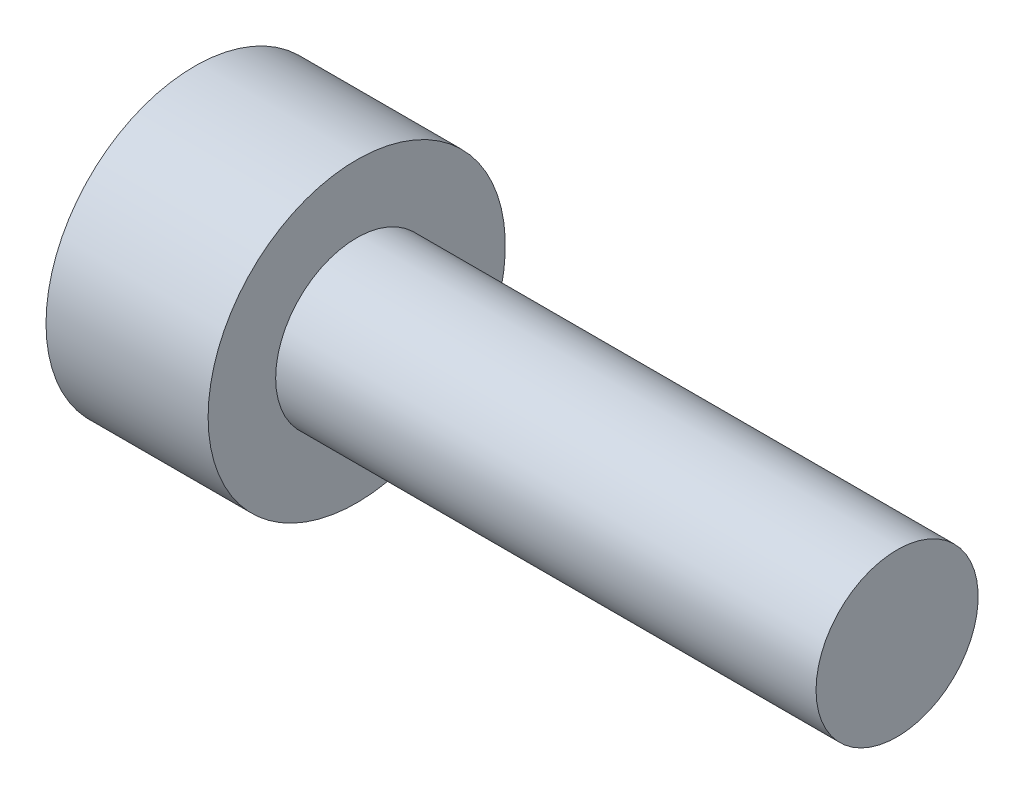
SolidWorks part; units mm, degrees
ref_plane "Front Plane" through (0, 0, 0) normal (0, 0, 1) x (1, 0, 0)
ref_plane "Top Plane" through (0, 0, 0) normal (0, 1, 0) x (1, 0, 0)
ref_plane "Right Plane" through (0, 0, 0) normal (1, 0, 0) x (0, 0, -1)
sketch "Screw Sketch" plane through (0, 0, 0) normal (0, 0, 1) x (1, 0, 0)
  line L0 (-1000, 0) -> (1000, 0) construction
  line L1 (-3, 0) -> (-3, 2.75)
  line L2 (-3, 2.75) -> (0, 2.75)
  line L3 (0, 2.75) -> (0, 1.5)
  line L4 (0, 1.5) -> (10, 1.5)
  line L5 (10, 1.5) -> (10, 0)
  line L6 (10, 0) -> (-3, 0)
revolve "Screw" add sketch "Screw Sketch" angle 360 about L0
ref_axis "Engine Axis" through (10.65, 0, 0) along (-1, 0, 0)
ref_plane "Head Top" through (-3, 0, 0) normal (1, 0, 0) x (0, 0, -1)
sketch "Socket Sketch" plane through (-3, 0, 0) normal (1, 0, 0) x (0, 0, -1)
  line L0 (1.4434, 0) -> (0.7217, 1.25)
  line L1 (0.7217, 1.25) -> (-0.7217, 1.25)
  line L2 (-0.7217, 1.25) -> (-1.4434, 0)
  line L3 (-1.4434, 0) -> (-0.7217, -1.25)
  line L4 (-0.7217, -1.25) -> (0.7217, -1.25)
  line L5 (0.7217, -1.25) -> (1.4434, 0)
extrude "Socket" cut sketch "Socket Sketch" along normal blind 1.5
